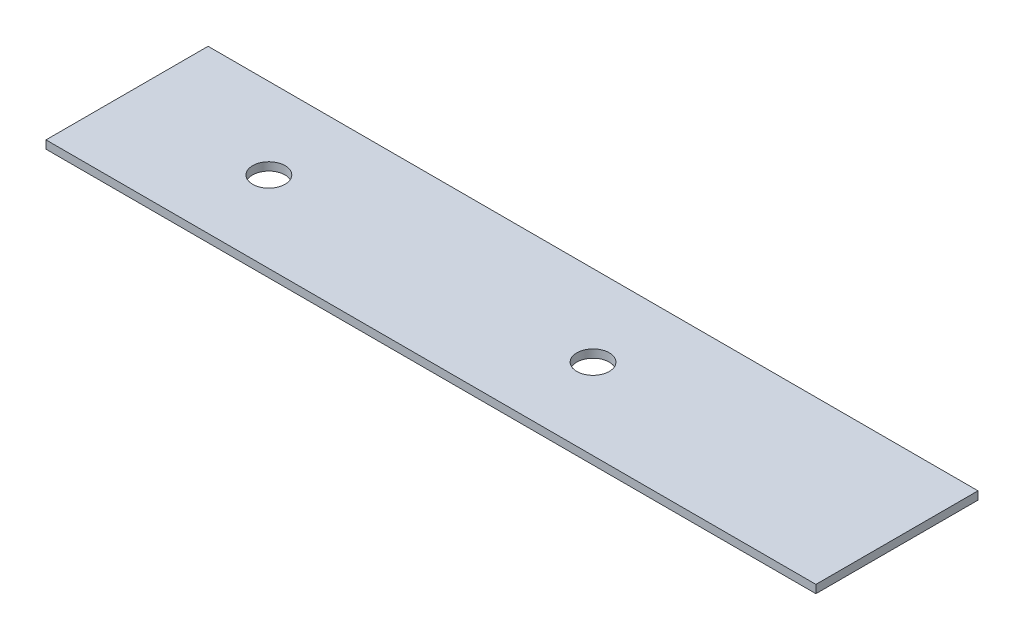
SolidWorks part; units mm, degrees
material "6061 Alloy"
ref_plane "Front Plane" through (0, 0, 0) normal (0, 0, 1) x (1, 0, 0)
ref_plane "Top Plane" through (0, 0, 0) normal (0, 1, 0) x (1, 0, 0)
ref_plane "Right Plane" through (0, 0, 0) normal (1, 0, 0) x (0, 0, -1)
sketch "Sketch1" plane through (0, 0, 0) normal (0, 1, 0) x (1, 0, 0)
  line L1 (-75, 20) -> (75, 20)
  line L2 (-75, 20) -> (-75, -20)
  line L3 (-75, -20) -> (75, -20)
  line L4 (75, 20) -> (75, -20)
  line L5 (-75, 20) -> (75, -20) construction
  line L6 (-75, -20) -> (75, 20) construction
  point P0 (0, 0)
  dimension "D1" = 40
  dimension "D2" = 150
sheet metal parameters "Sheet-Metal1" thickness 2 parameters "D1"=0.7366
base flange "Base-Flange1" sketch "Sketch1" thickness 2 reverse thickness direction no parameters "D1"=0.7366
sketch "Sketch4" plane through (0, 0, 0) normal (0, 1, 0) x (1, 0, 0)
  line L0 (0, 20) -> (0, -20) construction
  line L1 (75, 20) -> (-75, 20) construction
  line L2 (-75, -20) -> (75, -20) construction
  circle A0 centre (-40, 0) radius 4
  circle A1 centre (40, 0) radius 4
  dimension "D1" = 8
  dimension "D2" = 80
extrude "Cut-Extrude1" cut sketch "Sketch4" against normal through all normal cut yes
sketch "Sketch5" plane through (0, 0, 0) normal (0, 1, 0) x (1, 0, 0)
  line L1 (75, -20) -> (115, -20)
  line L2 (75, -20) -> (75, 20)
  line L3 (75, 20) -> (115, 20)
  line L4 (115, -20) -> (115, 20)
  dimension "D1" = 40
base flange "Tab1" sketch "Sketch5" thickness 2 reverse thickness direction no parameters "D1"=0.7366
sketch "Sketch6" plane through (0, 0, 0) normal (0, 1, 0) x (1, 0, 0)
  line L0 (40, 0) -> (60.0898, -74.976) construction
  line L1 (60.0898, -74.976) -> (45.359, -20)
  line L2 (-75, -20) -> (115, -20) construction
  line L3 (45.359, -20) -> (115, -20)
  line L4 (40, 0) -> (115, 0) construction
  line L5 (115, -20) -> (115, 20) construction
  arc A0 (115, -20) -> (60.0898, -74.976) centre (40, 0) cw
  dimension "D1" = 75
base flange "Tab3" [suppressed] sketch "Sketch6" thickness 2 reverse thickness direction no parameters "D1"=0.7366
flat pattern "Flat-Pattern1" [suppressed]
sketch "Bend-Lines1" plane through (0, 0, 0) normal (0, 1, 0) x (1, 0, 0)
sketch3d "Bounding-Box1" [suppressed]
  line L0 (-75, -20, 0) -> (75, -20, 0) construction
  line L1 (-75, 20, 0) -> (75, 20, 0) construction
  line L2 (-75, -20, 0) -> (-75, 20, 0) construction
  line L3 (75, -20, 0) -> (75, 20, 0) construction
